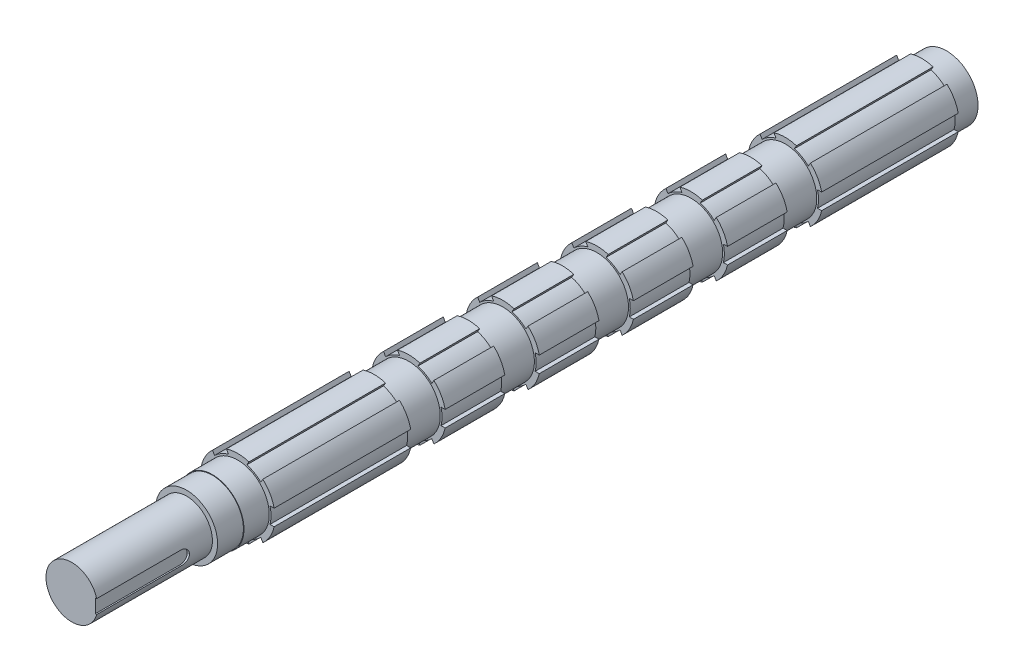
SolidWorks part; units mm, degrees
ref_plane "Front Plane" through (0, 0, 0) normal (0, 0, 1) x (1, 0, 0)
ref_plane "Top Plane" through (0, 0, 0) normal (0, 1, 0) x (1, 0, 0)
ref_plane "Right Plane" through (0, 0, 0) normal (1, 0, 0) x (0, 0, -1)
sketch "Sketch1" plane through (0, 0, 0) normal (0, 0, 1) x (1, 0, 0)
  circle A0 centre (0, 0) radius 32.5
  dimension "D1" = 65
extrude "Boss-Extrude1" add sketch "Sketch1" along normal blind 762
sketch "Sketch2" plane through (0, 0, 0) normal (0, 1, 0) x (1, 0, 0)
  line L0 (0, 0) -> (0, -1027.7466) construction
  line L1 (32.5, -762) -> (22.5, -762)
  line L2 (32.5, -762) -> (32.5, -662)
  line L3 (27, -662) -> (22.5, -662)
  line L4 (22.5, -762) -> (22.5, -662)
  line L5 (32.5, -762) -> (32.5, 0) construction
  line L7 (32.5, -662) -> (32.5, -639.5)
  line L8 (27.5, -639.5) -> (27, -639.5)
  line L9 (27, -662) -> (27, -639.5)
  line L11 (32.5, -639.5) -> (32.5, -617.5)
  line L12 (32.5, -617.5) -> (27.5, -617.5)
  line L13 (27.5, -639.5) -> (27.5, -617.5)
  line L14 (32.5, -498.5) -> (27.5, -498.5)
  line L15 (32.5, -498.5) -> (32.5, -468.5)
  line L16 (32.5, -468.5) -> (27.5, -468.5)
  line L17 (27.5, -498.5) -> (27.5, -468.5)
  line L19 (32.5, -416.5) -> (27.5, -416.5)
  line L20 (32.5, -416.5) -> (32.5, -386.5)
  line L21 (32.5, -386.5) -> (27.5, -386.5)
  line L22 (27.5, -416.5) -> (27.5, -386.5)
  line L23 (32.5, -334.5) -> (27.5, -334.5)
  line L24 (32.5, -334.5) -> (32.5, -304.5)
  line L25 (32.5, -304.5) -> (27.5, -304.5)
  line L26 (27.5, -334.5) -> (27.5, -304.5)
  line L27 (32.5, -252.5) -> (27.5, -252.5)
  line L28 (32.5, -252.5) -> (32.5, -222.5)
  line L29 (32.5, -222.5) -> (27.5, -222.5)
  line L30 (27.5, -252.5) -> (27.5, -222.5)
  line L31 (32.5, -170.5) -> (27.5, -170.5)
  line L32 (32.5, -170.5) -> (32.5, -140.5)
  line L33 (32.5, -140.5) -> (27.5, -140.5)
  line L34 (27.5, -170.5) -> (27.5, -140.5)
  line L35 (32.5, 0) -> (27.5, 0)
  line L36 (32.5, 0) -> (32.5, -21.5)
  line L37 (32.5, -21.5) -> (27.5, -21.5)
  line L38 (27.5, 0) -> (27.5, -21.5)
  point P24 (30, -416.5)
  dimension "D1" = 22.5
  dimension "D2" = 100
  dimension "D3" = 27
  dimension "D4" = 22.5
  dimension "D5" = 27.5
  dimension "D6" = 22
  dimension "D7" = 27.5
  dimension "D8" = 119
  dimension "D9" = 30
  dimension "D10" = 27.5
  dimension "D11" = 52
  dimension "D12" = 30
  dimension "D13" = 52
  dimension "D14" = 30
  dimension "D15" = 52
  dimension "D16" = 30
  dimension "D17" = 52
  dimension "D18" = 30
  dimension "D19" = 119
revolve "Cut-Revolve1" cut sketch "Sketch2" angle 360 about L0
sketch "Sketch3" plane through (0, 0, 0) normal (0, 0, -1) x (-1, 0, 0)
  line L0 (31.7372, 7) -> (28.1425, 7)
  line L1 (31.7372, -7) -> (28.1425, -7)
  arc A0 (31.7372, -7) -> (31.7372, 7) centre (0, 0) ccw
  arc A1 (28.1425, -7) -> (28.1425, 7) centre (0, 0) ccw
  dimension "D1" = 58
  dimension "D2" = 65
  dimension "D3" = 7
  dimension "D4" = 14
extrude "Cut-Extrude1" cut sketch "Sketch3" against normal blind 762
pattern_circular "CirPattern1" count 6 over 360 about axis through (0, 0, 762) along (0, 0, -1) of "Cut-Extrude1" reverse direction yes
sketch "Sketch4" plane through (0, 0, 762) normal (0, 0, 1) x (1, 0, 0)
  line L0 (20.5, 6) -> (20.5, -6)
  line L1 (20.5, 6) -> (21.6852, 6)
  line L2 (20.5, -6) -> (21.6852, -6)
  arc A0 (21.6852, -6) -> (21.6852, 6) centre (0, 0) ccw
  dimension "D4" = 45
  dimension "D1" = 12
  dimension "D2" = 6
  dimension "D3" = 20.5
extrude "Cut-Extrude2" cut sketch "Sketch4" against normal blind 80
fillet "Fillet1" radius 6 2 edges at (21.0926, 6, 682) (21.0926, -6, 682)
